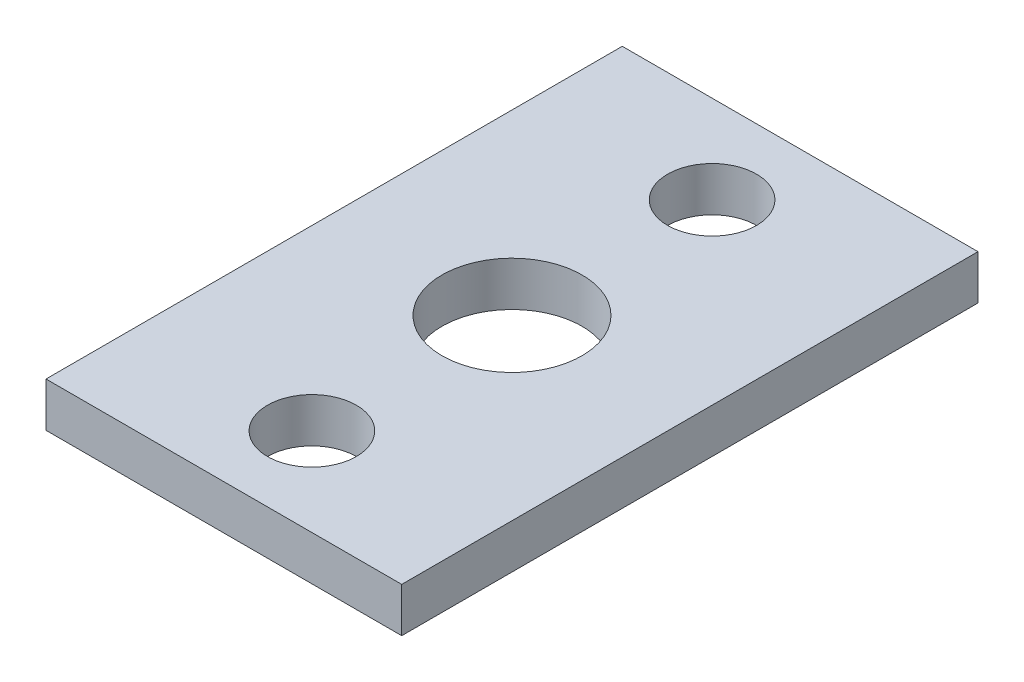
SolidWorks part; units mm, degrees
ref_plane "Front Plane" through (0, 0, 0) normal (0, 0, 1) x (1, 0, 0)
ref_plane "Top Plane" through (0, 0, 0) normal (0, 1, 0) x (1, 0, 0)
ref_plane "Right Plane" through (0, 0, 0) normal (1, 0, 0) x (0, 0, -1)
sketch "Sketch1" plane through (0, 0, 0) normal (0, 1, 0) x (1, 0, 0)
  line L1 (-6.35, 10.287) -> (6.35, 10.287)
  line L2 (-6.35, 10.287) -> (-6.35, -10.287)
  line L3 (-6.35, -10.287) -> (6.35, -10.287)
  line L4 (6.35, 10.287) -> (6.35, -10.287)
  dimension "D1" = 20.574
  dimension "D2" = 12.7
extrude "Extrude1" add sketch "Sketch1" along normal blind 1.5875
sketch "Sketch3" plane through (0, 0, 0) normal (0, 1, 0) x (1, 0, 0)
  circle A0 centre (0, 7.1437) radius 1.5875
  dimension "D1" = 3.175
  dimension "D2" = 7.1437
extrude "Cut-Extrude6" cut sketch "Sketch3" along normal through all
ref_axis "Axis1" through (0, 8.7766, 0) along (0, -1, 0)
pattern_circular "CirPattern1" count 2 over 360 about axis through (0, 8.7766, 0) along (0, -1, 0) of "Cut-Extrude6"
sketch "Sketch4" plane through (0, 0, 0) normal (0, 1, 0) x (1, 0, 0)
  circle A0 centre (0, 7.1437) radius 2.3241
  dimension "D1" = 4.6482
sketch "Sketch5" plane through (0, 0, 0) normal (0, 1, 0) x (1, 0, 0)
  circle A0 centre (0, 0) radius 2.5
  dimension "D1" = 5
extrude "Cut-Extrude8" cut sketch "Sketch5" along normal through all
sketch "Sketch6" plane through (0, 0, 0) normal (0, 1, 0) x (1, 0, 0)
  point P0 (0, 0)
